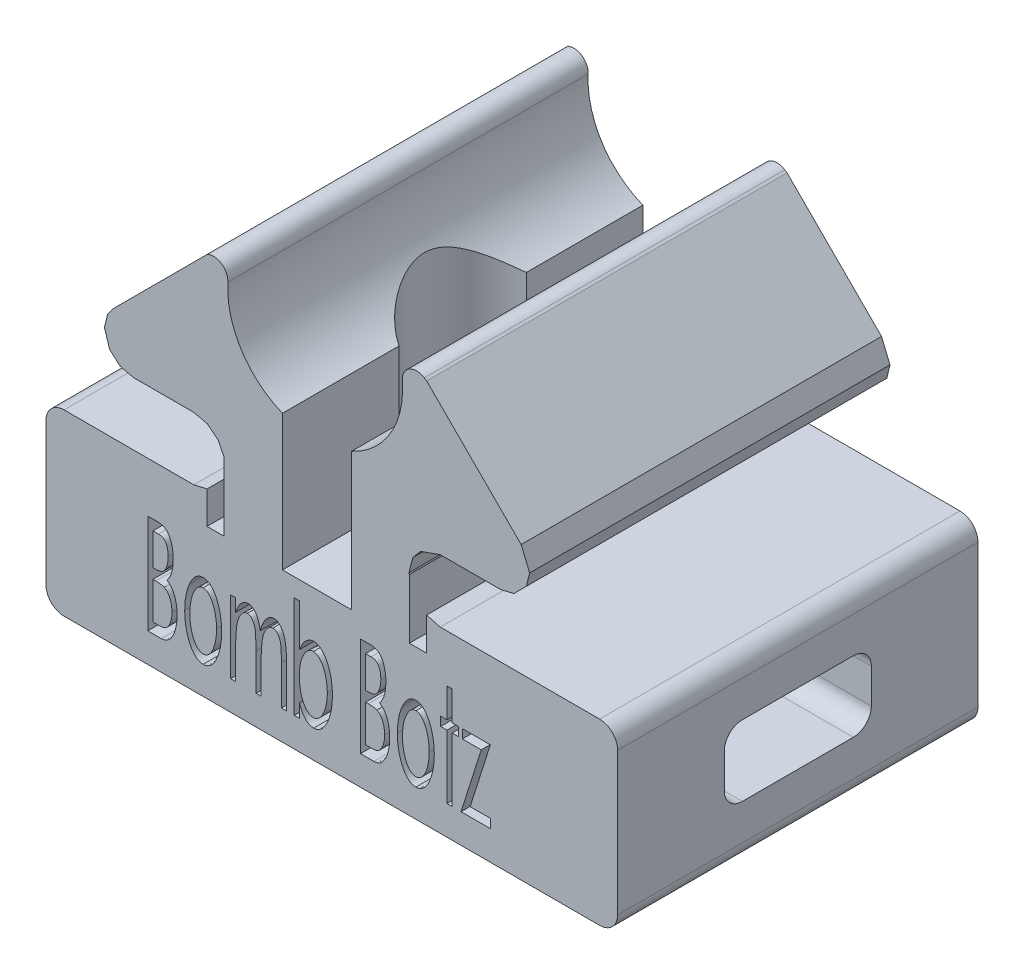
SolidWorks part; units mm, degrees
ref_plane "Front Plane" through (0, 0, 0) normal (0, 0, 1) x (1, 0, 0)
ref_plane "Top Plane" through (0, 0, 0) normal (0, 1, 0) x (1, 0, 0)
ref_plane "Right Plane" through (0, 0, 0) normal (1, 0, 0) x (0, 0, -1)
sketch "Sketch5" plane through (0, 0, 0) normal (0, 0, 1) x (1, 0, 0)
  line L0 (-6.4748, -10.4902) -> (-6.9383, -10.3783)
  line L1 (-6.9383, -10.3783) -> (-7.3088, -10.0545)
  line L2 (-7.3088, -10.0545) -> (-7.4908, -9.4742)
  line L3 (-7.4908, -9.4742) -> (-7.3789, -9.0107)
  line L4 (-7.3789, -9.0107) -> (-7.1932, -8.7558)
  line L5 (-7.1932, -8.7558) -> (-3.8632, -5.4257)
  line L6 (-3.8632, -5.4257) -> (-2.8331, -4.7375)
  line L7 (-2.8331, -4.7375) -> (-1.6181, -4.4958)
  line L8 (-1.6181, -4.4958) -> (1.6181, -4.4958)
  line L9 (1.6181, -4.4958) -> (2.6682, -4.6745)
  line L10 (2.6682, -4.6745) -> (3.8632, -5.4257)
  line L11 (3.8632, -5.4257) -> (7.1932, -8.7558)
  line L12 (7.1932, -8.7558) -> (7.4908, -9.4742)
  line L13 (7.4908, -9.4742) -> (7.3789, -9.9377)
  line L14 (6.4748, -10.4902) -> (6.9383, -10.3783)
  line L15 (6.9383, -10.3783) -> (7.3789, -9.9377)
  line L16 (6.4748, -10.4902) -> (4.3434, -10.4902)
  line L19 (-6.4748, -10.4902) -> (-4.3434, -10.4902)
  line L20 (-4.3434, -10.4902) -> (-3.8632, -10.6)
  line L21 (-3.8632, -10.6) -> (-3.486, -10.8982)
  line L22 (-3.486, -10.8982) -> (-3.2711, -11.3288)
  line L23 (-3.2711, -11.3288) -> (-3.2711, -11.8614)
  line L24 (-3.2711, -11.8614) -> (-3.486, -12.292)
  line L25 (-3.486, -12.292) -> (-3.8632, -12.5902)
  line L26 (-3.8632, -12.5902) -> (-4.3434, -12.7)
  line L27 (-4.3434, -12.7) -> (-9.5504, -12.7)
  line L28 (-9.5504, -12.7) -> (-9.5504, -18.9956)
  line L29 (-9.5504, -18.9956) -> (10.5918, -18.9956)
  line L30 (10.5918, -18.9956) -> (10.5918, -12.7)
  line L31 (10.5918, -12.7) -> (4.3434, -12.7)
  line L32 (4.3434, -12.7) -> (3.8076, -12.5614)
  line L33 (3.8076, -12.5614) -> (3.486, -12.292)
  line L34 (3.486, -12.292) -> (3.2385, -11.5951)
  line L35 (3.2385, -11.5951) -> (3.3771, -11.0593)
  line L36 (3.3771, -11.0593) -> (3.6465, -10.7377)
  line L37 (3.6465, -10.7377) -> (4.3434, -10.4902)
extrude "Boss-Extrude1" add sketch "Sketch5" against normal blind 12.7
sketch "Sketch10" plane through (0, 0, 0) normal (0, 0, 1) x (1, 0, 0)
  circle A0 centre (-0.0665, -6.096) radius 3.0821
extrude "Cut-Extrude1" cut sketch "Sketch10" against normal through all
sketch "Sketch11" plane through (0, 0, 0) normal (0, 0, 1) x (1, 0, 0)
  line L1 (-1.2179, -5.8277) -> (1.2179, -5.8277)
  line L2 (-1.2179, -5.8277) -> (-1.2179, -13.7361)
  line L3 (-1.2179, -13.7361) -> (1.2179, -13.7361)
  line L4 (1.2179, -5.8277) -> (1.2179, -13.7361)
  line L5 (-1.2179, -5.8277) -> (1.2179, -13.7361) construction
  line L6 (-1.2179, -13.7361) -> (1.2179, -5.8277) construction
  point P0 (0, -9.7819)
extrude "Cut-Extrude2" cut sketch "Sketch11" against normal through all
sketch "Sketch13" plane through (-9.5504, 0, 0) normal (-1, 0, 0) x (0, 0, 1)
  line L1 (-8.941, -14.6031) -> (-3.759, -14.6031)
  line L2 (-8.941, -14.6031) -> (-8.941, -17.0925)
  line L3 (-8.941, -17.0925) -> (-3.759, -17.0925)
  line L4 (-3.759, -14.6031) -> (-3.759, -17.0925)
  line L5 (-8.941, -14.6031) -> (-3.759, -17.0925) construction
  line L6 (-8.941, -17.0925) -> (-3.759, -14.6031) construction
  point P0 (-6.35, -15.8478)
extrude "Cut-Extrude4" cut sketch "Sketch13" against normal through all
fillet "Fillet1" radius 0.635 1 edges at (-9.5504, -12.7, -6.35)
fillet "Fillet2" radius 0.635 7 edges at (10.5918, -18.9956, -6.35) (10.5918, -12.7, -6.35) (0.5207, -14.6031, -3.759) (-9.5504, -18.9956, -6.35) (0.5207, -17.0925, -3.759) (0.5207, -17.0925, -8.941) (0.5207, -14.6031, -8.941)
fillet "Fillet3" radius 0.508 2 edges at (2.6682, -4.6745, -6.35) (-2.8331, -4.7375, -6.35)
sketch "Sketch15" plane through (0, 0, 0) normal (0, 0, 1) x (1, 0, 0)
  text T0 "Bomb Botz" font "Century Gothic" height 3.5
extrude "Cut-Extrude5" cut sketch "Sketch15" against normal blind 1.27
sketch "Sketch17" plane through (0, 0, 0) normal (0, 0, 1) x (1, 0, 0)
  line L0 (3.486, -12.292) -> (3.2385, -11.5951) construction
  line L1 (3.2547, -11.6407) -> (3.8597, -11.6407)
  line L2 (3.2547, -11.6407) -> (3.2547, -13.7361)
  line L3 (3.2547, -13.7361) -> (3.8597, -13.7361)
  line L4 (3.8597, -11.6407) -> (3.8597, -13.7361)
  line L5 (-3.2711, -11.3288) -> (-3.2711, -11.8614) construction
  line L6 (-3.2711, -11.5951) -> (-3.8755, -11.5951)
  line L7 (-3.2711, -11.5951) -> (-3.2711, -13.7361)
  line L8 (-3.2711, -13.7361) -> (-3.8755, -13.7361)
  line L9 (-3.8755, -11.5951) -> (-3.8755, -13.7361)
extrude "Cut-Extrude7" cut sketch "Sketch17" against normal through all
sketch "Sketch18" plane through (0, -18.9956, 0) normal (0, -1, 0) x (-1, 0, 0)
  line L0 (8.9154, 0) -> (-9.9568, 0) construction
  line L1 (9.5504, 12.7) -> (9.5504, 0) construction
  circle A0 centre (0.0254, 6.35) radius 2.54
  dimension "D1" = 5.08
  dimension "D2" = 6.35
  dimension "D3" = 9.525
extrude "Cut-Extrude8" cut sketch "Sketch18" against normal through all
